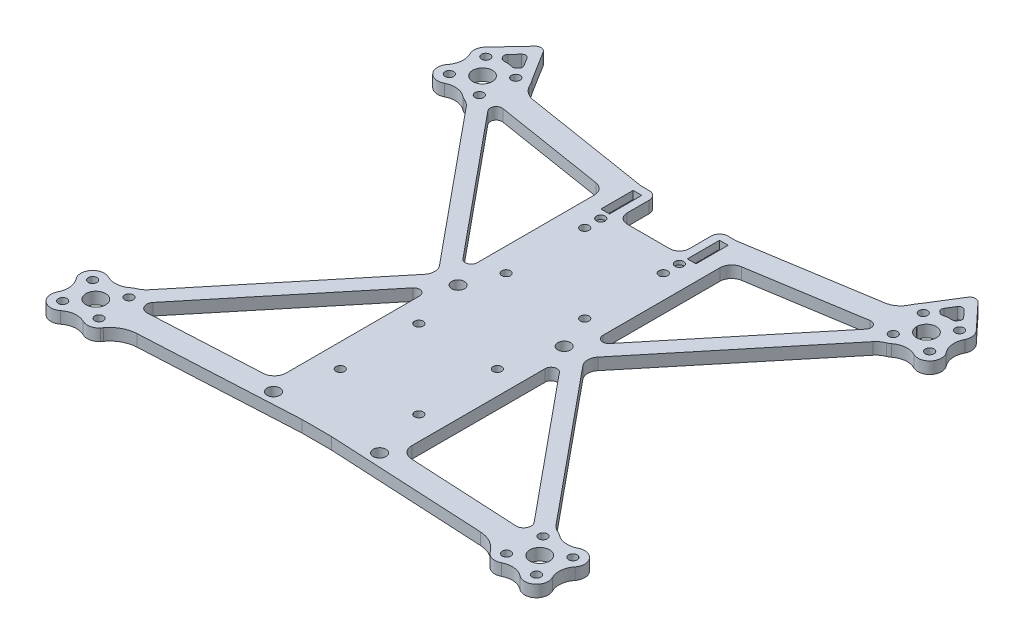
SolidWorks part; units mm, degrees
ref_plane "Front Plane" through (0, 0, 0) normal (0, 0, 1) x (1, 0, 0)
ref_plane "Top Plane" through (0, 0, 0) normal (0, 1, 0) x (1, 0, 0)
ref_plane "Right Plane" through (0, 0, 0) normal (1, 0, 0) x (0, 0, -1)
sketch "Sketch1" plane through (0, 0, 0) normal (0, 1, 0) x (1, 0, 0)
  line L0 (0, 42.225) -> (0, -42.225) construction
  line L1 (16, 42.225) -> (-16, 42.225)
  line L2 (16, 42.225) -> (16, -42.225)
  line L3 (16, -42.225) -> (-16, -42.225)
  line L4 (-16, 42.225) -> (-16, -42.225)
  line L5 (16, 42.225) -> (-16, -42.225) construction
  line L6 (16, -42.225) -> (-16, 42.225) construction
  line L12 (-12.1, 50.425) -> (-12.1, 52.425) construction
  line L17 (-11, 52.425) -> (-11, 42.225) construction
  line L18 (-7.9, 42.225) -> (-14.1, 42.225)
  line L20 (-10, 36) -> (10, 36)
  line L21 (-10, 36) -> (-10, 16)
  line L22 (-10, 16) -> (10, 16)
  line L23 (10, 36) -> (10, 16)
  line L24 (-10, 36) -> (10, 16) construction
  line L25 (-10, 16) -> (10, 36) construction
  line L26 (-14.5, 10.775) -> (14.5, 10.775)
  line L27 (-14.5, 10.775) -> (-14.5, 41.225)
  line L28 (-14.5, 41.225) -> (14.5, 41.225)
  line L29 (14.5, 10.775) -> (14.5, 41.225)
  line L30 (-14.5, 10.775) -> (14.5, 41.225) construction
  line L31 (-14.5, 41.225) -> (14.5, 10.775) construction
  line L32 (-10, -6.225) -> (10, -6.225)
  line L33 (-10, -6.225) -> (-10, -26.225)
  line L34 (-10, -26.225) -> (10, -26.225)
  line L35 (10, -6.225) -> (10, -26.225)
  line L36 (-10, -6.225) -> (10, -26.225) construction
  line L37 (-10, -26.225) -> (10, -6.225) construction
  line L38 (-15.75, -36.225) -> (15.75, -36.225)
  line L39 (-15.75, -36.225) -> (-15.75, 3.775)
  line L40 (-15.75, 3.775) -> (15.75, 3.775)
  line L41 (15.75, -36.225) -> (15.75, 3.775)
  line L42 (-15.75, -36.225) -> (15.75, 3.775) construction
  line L43 (-15.75, 3.775) -> (15.75, -36.225) construction
  line L48 (-7.9, 42.225) -> (-7.9, 52.425)
  line L49 (-7.9, 52.425) -> (-14.1, 52.425)
  line L59 (-14.1, 42.225) -> (-14.1, 52.425)
  line L63 (-12.1, 50.425) -> (-9.9, 50.425)
  line L64 (-12.1, 50.425) -> (-12.1, 42.225)
  line L65 (-12.1, 42.225) -> (-9.9, 42.225)
  line L66 (-9.9, 50.425) -> (-9.9, 42.225)
  line L67 (-12.1, 50.425) -> (-9.9, 42.225) construction
  line L68 (-12.1, 42.225) -> (-9.9, 50.425) construction
  line L69 (-12.1, 50.425) -> (-14.1, 50.425) construction
  line L74 (7.9, 42.225) -> (14.1, 42.225)
  line L75 (14.1, 42.225) -> (14.1, 52.425)
  line L76 (7.9, 52.425) -> (14.1, 52.425)
  line L77 (7.9, 42.225) -> (7.9, 52.425)
  line L78 (12.1, 50.425) -> (9.9, 50.425)
  line L79 (12.1, 50.425) -> (12.1, 42.225)
  line L80 (12.1, 42.225) -> (9.9, 42.225)
  line L81 (9.9, 50.425) -> (9.9, 42.225)
  line L82 (-14.5, 10.775) -> (-14.5, 3.775) construction
  line L83 (-14.5, 7.275) -> (16, 7.275) construction
  line L89 (-13.5, -37.225) -> (-16, -37.225) construction
  line L94 (-14.1, 52.425) -> (-16, 52.425)
  line L95 (-14.1, 52.425) -> (-14.1, 42.225)
  line L96 (-14.1, 42.225) -> (-16, 42.225)
  line L97 (-16, 52.425) -> (-16, 42.225)
  line L98 (14.1, 52.425) -> (16, 52.425)
  line L99 (14.1, 52.425) -> (14.1, 42.225)
  line L100 (14.1, 42.225) -> (16, 42.225)
  line L101 (16, 52.425) -> (16, 42.225)
  circle A3 centre (-10, 36) radius 1.1
  circle A4 centre (10, 36) radius 1.1
  circle A5 centre (10, 16) radius 1.1
  circle A6 centre (-10, 16) radius 1.1
  circle A7 centre (-10, -6.225) radius 1.1
  circle A8 centre (10, -6.225) radius 1.1
  circle A9 centre (10, -26.225) radius 1.1
  circle A10 centre (-10, -26.225) radius 1.1
  circle A37 centre (-13.5, 7.275) radius 2.5
  circle A38 centre (-13.5, 7.275) radius 1.625
  circle A39 centre (13.5, 7.275) radius 1.625
  circle A40 centre (-13.5, -39.725) radius 2.5
  circle A41 centre (-13.5, -39.725) radius 1.625
  circle A42 centre (13.5, -39.725) radius 1.625
  point P0 (0, 0)
  point P8 (0, 0)
  point P16 (0, 26)
  point P26 (0, 26)
  point P31 (0, -16.225)
  point P36 (0, -16.225)
  point P61 (-11, 46.325)
  dimension "D3" = 2
  dimension "D17" = 2.2
  dimension "D22" = 5
  dimension "D23" = 3.25
  dimension "D8" = 32
  dimension "D9" = 22
  dimension "D10" = 20
  dimension "D11" = 29
  dimension "D12" = 30.45
  dimension "D13" = 40
  dimension "D14" = 31.5
  dimension "D15" = 1
  dimension "D16" = 7
  dimension "D18" = 2.2
  dimension "D20" = 8.2
  dimension "D24" = 1
extrude "Base shape" add sketch "Sketch1" along normal blind 2 contours L63 L66 L1 L48 L49 L59 L18 L64 | L81 L78 L79 L1 L75 L76 L77 | L94 L97 L1 L59 | L101 L98 L75 L1 | L1 L4 L3 L2 | A4 | A3 | A7 | A8 | A9 | A10 | A5 | A6 | A39 | A38 | A41 | A42 region at (15.05, 0, -47.325) region at (13.1, 0, -42.3444) region at (-8.9, 0, -42.3444) region at (-15.05, 0, -47.325)
sketch "Sketch2" plane through (0, 0, 0) normal (0, -1, 0) x (1, 0, 0)
  line L0 (-12.1, -42.225) -> (-9.9, -50.425) construction
  line L1 (12.1, -42.225) -> (9.9, -50.425) construction
  line L4 (12.1, -42.225) -> (9.9, -42.225)
  line L5 (12.1, -50.425) -> (12.1, -42.225)
  line L6 (9.9, -50.425) -> (12.1, -50.425)
  line L7 (9.9, -42.225) -> (9.9, -50.425)
  line L8 (12.1, -42.225) -> (9.9, -42.225)
  line L9 (12.1, -50.425) -> (12.1, -42.225)
  line L10 (9.9, -50.425) -> (12.1, -50.425)
  line L11 (9.9, -42.225) -> (9.9, -50.425)
  line L12 (-9.9, -42.225) -> (-12.1, -42.225)
  line L13 (-9.9, -50.425) -> (-9.9, -42.225)
  line L14 (-12.1, -50.425) -> (-9.9, -50.425)
  line L15 (-12.1, -42.225) -> (-12.1, -50.425)
  line L16 (-9.9, -42.225) -> (-12.1, -42.225)
  line L17 (-9.9, -50.425) -> (-9.9, -42.225)
  line L18 (-12.1, -50.425) -> (-9.9, -50.425)
  line L19 (-12.1, -42.225) -> (-12.1, -50.425)
  circle A0 centre (-11, -46.325) radius 1.1
  circle A1 centre (11, -46.325) radius 1.1
  dimension "D1" = 0
  dimension "D2" = 0
extrude "Camera mount pockets" add sketch "Sketch2" against normal offset from surface (1 mm away) 1 contours A0 L19 | A0 L17 | A1 L9 | A1 L11 region at (11, 0, -43.8523) region at (11, 0, -48.7977) region at (-11, 0, -43.8523) region at (-11, 0, -48.7977) up to face at (11, 2, -46.325)
fillet "Main fillets" radius 2.5 6 edges at (7.9, 1, -42.225) (-7.9, 1, -42.225) (-16, 1, -52.425) (16, 1, -52.425) (-16, 1, 42.225) (16, 1, 42.225)
fillet "Inner camera mount fillets" radius 2.1 2 edges at (-7.9, 1, -52.425) (7.9, 1, -52.425)
sketch "Sketch3" plane through (0, 2, 0) normal (0, 1, 0) x (1, 0, 0)
  line L6 (12.1, 42.225) -> (12.1, 50.425)
  line L7 (9.9, 42.225) -> (12.1, 42.225)
  line L8 (-10, 52.425) -> (-13.5, 52.425)
  line L9 (-16, 49.925) -> (-16, -39.725)
  line L10 (-13.5, -42.225) -> (13.5, -42.225)
  line L11 (16, -39.725) -> (16, 49.925)
  line L12 (13.5, 52.425) -> (10, 52.425)
  line L13 (7.9, 50.325) -> (7.9, 44.725)
  line L14 (5.4, 42.225) -> (-5.4, 42.225)
  line L15 (-7.9, 44.725) -> (-7.9, 50.325)
  line L16 (-10, 52.425) -> (-13.5, 52.425)
  line L17 (-16, 49.925) -> (-16, -39.725)
  line L18 (-13.5, -42.225) -> (13.5, -42.225)
  line L19 (16, -39.725) -> (16, 49.925)
  line L20 (13.5, 52.425) -> (10, 52.425)
  line L21 (7.9, 50.325) -> (7.9, 44.725)
  line L22 (5.4, 42.225) -> (-5.4, 42.225)
  line L23 (-7.9, 44.725) -> (-7.9, 50.325)
  line L24 (9.9, 50.425) -> (9.9, 42.225)
  line L25 (12.1, 50.425) -> (9.9, 50.425)
  line L26 (12.1, 42.225) -> (12.1, 50.425)
  line L27 (9.9, 42.225) -> (12.1, 42.225)
  line L28 (9.9, 50.425) -> (9.9, 42.225)
  line L29 (12.1, 50.425) -> (9.9, 50.425)
  line L30 (-9.9, 42.225) -> (-9.9, 50.425)
  line L31 (-12.1, 42.225) -> (-9.9, 42.225)
  line L32 (-12.1, 50.425) -> (-12.1, 42.225)
  line L33 (-9.9, 50.425) -> (-12.1, 50.425)
  line L34 (-9.9, 42.225) -> (-9.9, 50.425)
  line L35 (-12.1, 42.225) -> (-9.9, 42.225)
  line L36 (-12.1, 50.425) -> (-12.1, 42.225)
  line L37 (-9.9, 50.425) -> (-12.1, 50.425)
  circle A0 centre (13.5, -39.725) radius 1.625 construction
  circle A1 centre (-13.5, -39.725) radius 1.625 construction
  circle A2 centre (-13.5, 7.275) radius 1.625 construction
  circle A3 centre (-10, -6.225) radius 1.1 construction
  circle A4 centre (-10, -26.225) radius 1.1 construction
  circle A5 centre (10, -26.225) radius 1.1 construction
  circle A6 centre (10, -6.225) radius 1.1 construction
  circle A7 centre (13.5, 7.275) radius 1.625 construction
  arc A8 (-13.5, 52.425) -> (-16, 49.925) centre (-13.5, 49.925) ccw
  arc A9 (-16, -39.725) -> (-13.5, -42.225) centre (-13.5, -39.725) ccw
  arc A10 (13.5, -42.225) -> (16, -39.725) centre (13.5, -39.725) ccw
  arc A11 (16, 49.925) -> (13.5, 52.425) centre (13.5, 49.925) ccw
  arc A12 (-7.9, 50.325) -> (-10, 52.425) centre (-10, 50.325) ccw
  arc A13 (5.4, 42.225) -> (7.9, 44.725) centre (5.4, 44.725) ccw
  arc A14 (-7.9, 44.725) -> (-5.4, 42.225) centre (-5.4, 44.725) ccw
  arc A15 (-7.9, 50.325) -> (-10, 52.425) centre (-10, 50.325) ccw
  arc A16 (-13.5, 52.425) -> (-16, 49.925) centre (-13.5, 49.925) ccw
  arc A17 (-16, -39.725) -> (-13.5, -42.225) centre (-13.5, -39.725) ccw
  arc A18 (13.5, -42.225) -> (16, -39.725) centre (13.5, -39.725) ccw
  arc A19 (16, 49.925) -> (13.5, 52.425) centre (13.5, 49.925) ccw
  arc A21 (5.4, 42.225) -> (7.9, 44.725) centre (5.4, 44.725) ccw
  arc A22 (-7.9, 44.725) -> (-5.4, 42.225) centre (-5.4, 44.725) ccw
  circle A24 centre (-10, 16) radius 1.1 construction
  circle A25 centre (-10, 36) radius 1.1 construction
  circle A26 centre (10, 36) radius 1.1 construction
  circle A27 centre (10, 16) radius 1.1 construction
  circle A28 centre (10, 16) radius 1.1
  circle A29 centre (10, 36) radius 1.1
  circle A30 centre (-10, 36) radius 1.1
  circle A31 centre (-10, 16) radius 1.1
  circle A32 centre (13.5, 7.275) radius 1.625
  circle A33 centre (10, -6.225) radius 1.1
  circle A34 centre (10, -26.225) radius 1.1
  circle A35 centre (-10, -26.225) radius 1.1
  circle A36 centre (-10, -6.225) radius 1.1
  circle A37 centre (13.5, -39.725) radius 1.625
  circle A38 centre (-13.5, -39.725) radius 1.625
  circle A39 centre (-13.5, 7.275) radius 1.625
  arc A48 (10, 52.425) -> (7.9, 50.325) centre (10, 50.325) ccw
  arc A49 (10, 52.425) -> (7.9, 50.325) centre (10, 50.325) ccw
  dimension "D1" = 0
  dimension "D2" = 0
  dimension "D3" = 0
extrude "Thicker base" add sketch "Sketch3" along normal blind 1
sketch "Sketch4" plane through (0, 0, 0) normal (0, -1, 0) x (1, 0, 0)
  line L0 (0, 13.9568) -> (0, -8.6953) construction
  line L1 (-14.1, -38.5) -> (-5.9, -38.5)
  line L2 (-14.1, -38.5) -> (-14.1, -41.7)
  line L3 (-14.1, -41.7) -> (-5.9, -41.7)
  line L4 (-5.9, -38.5) -> (-5.9, -41.7)
  line L5 (-10, -38.5) -> (-10, -41.7) construction
  line L7 (14.1, -38.5) -> (5.9, -38.5)
  line L8 (14.1, -38.5) -> (14.1, -41.7)
  line L9 (14.1, -41.7) -> (5.9, -41.7)
  line L10 (5.9, -38.5) -> (5.9, -41.7)
  line L11 (-14.1, -38.5) -> (-10.9, -41.7) construction
  line L12 (-14.1, -40.1) -> (-5.9, -40.1) construction
  circle A0 centre (-10, -36) radius 2
  circle A1 centre (-13.3929, -39.2071) radius 1
  circle A2 centre (-13.3929, -40.9929) radius 1
  circle A3 centre (-6.6071, -39.2071) radius 1
  circle A4 centre (-6.6071, -40.9929) radius 1
  circle A5 centre (6.6071, -40.9929) radius 1
  circle A6 centre (6.6071, -39.2071) radius 1
  circle A7 centre (13.3929, -39.2071) radius 1
  circle A8 centre (13.3929, -40.9929) radius 1
  point P9 (-10, -38)
  dimension "D5" = 4
  dimension "D7" = 2
  dimension "D1" = 8.2
  dimension "D2" = 3.2
  dimension "D3" = 10
  dimension "D4" = 0.5
  dimension "D6" = 45
extrude "Battery holder pockets" cut sketch "Sketch4" against normal offset from surface (2 mm away) 1 contours A2 L2 | A2 L3 | L2 A1 | L1 A1 | A3 L4 | A3 L1 | L4 A4 | L3 A4 | A5 L9 | A5 L10 | L10 A6 | L7 A6 | A7 L7 | A7 L8 | L8 A8 | L9 A8 | L3 L4 L1 L2 | L9 L10 L7 L8 region at (-13.3929, 0, -38.3812) region at (-14.2188, 0, -39.2071) region at (-6.6071, 0, -38.3812) region at (-14.2188, 0, -40.9929) region at (-5.7812, 0, -39.2071) region at (-13.3929, 0, -41.8188) region at (-6.6071, 0, -41.8188) region at (-5.7812, 0, -40.9929) region at (14.2188, 0, -39.2071) region at (13.3929, 0, -38.3812) region at (6.6071, 0, -38.3812) region at (14.2188, 0, -40.9929) region at (5.7812, 0, -39.2071) region at (13.3929, 0, -41.8188) region at (6.6071, 0, -41.8188) region at (5.7812, 0, -40.9929) up to face at (-13.5, 3, 41.35)
sketch "Sketch5" plane through (0, 2, 0) normal (0, -1, 0) x (1, 0, 0)
  line L0 (-10, -38.5) -> (-10, -41.7) construction
  line L1 (-12.6858, -38.5) -> (-7.3142, -38.5) construction
  line L2 (-12.6858, -41.7) -> (-7.3142, -41.7) construction
  line L3 (0, 5.9884) -> (0, -5.6723) construction
  circle A0 centre (-10, -40.1) radius 1.1
  circle A1 centre (10, -40.1) radius 1.1
  dimension "D1" = 2.2
extrude "Battery holder holes" cut sketch "Sketch5" against normal up to next
sketch "Sketch6" [suppressed] plane through (0, 0, 0) normal (0, -1, 0) x (1, 0, 0)
  line L0 (0, -5.1) -> (0, 9.653) construction
  line L8 (-13.5, -7.275) -> (13.5, -7.275) construction
  line L10 (-16, -25.775) -> (16, -25.775) construction
  line L11 (-16, -49.925) -> (-16, 39.725) construction
  line L12 (16, -49.925) -> (16, 39.725) construction
  line L13 (17.5, -34.275) -> (19, -34.275)
  line L14 (16, -37.275) -> (19, -37.275)
  line L15 (16, -37.275) -> (16, -14.275)
  line L16 (16, -14.275) -> (19, -14.275)
  line L17 (19, -37.275) -> (19, -14.275)
  line L18 (16, -37.275) -> (19, -14.275) construction
  line L19 (16, -14.275) -> (19, -37.275) construction
  line L20 (16, -35.775) -> (17.5, -35.775)
  line L21 (16, -35.775) -> (16, -15.775)
  line L22 (16, -15.775) -> (17.5, -15.775)
  line L23 (17.5, -35.775) -> (17.5, -15.775)
  line L24 (16, -35.775) -> (17.5, -15.775) construction
  line L25 (16, -15.775) -> (17.5, -35.775) construction
  line L26 (17.5, -17.275) -> (19, -17.275)
  line L27 (-17.5, -34.275) -> (-19, -34.275)
  line L28 (-17.5, -17.275) -> (-19, -17.275)
  line L29 (-16, -35.775) -> (-16, -15.775)
  line L30 (-16, -35.775) -> (-17.5, -35.775)
  line L31 (-17.5, -35.775) -> (-17.5, -15.775)
  line L32 (-16, -15.775) -> (-17.5, -15.775)
  line L33 (-16, -37.275) -> (-16, -14.275)
  line L34 (-16, -37.275) -> (-19, -37.275)
  line L35 (-19, -37.275) -> (-19, -14.275)
  line L36 (-16, -14.275) -> (-19, -14.275)
  line L37 (16, 22.725) -> (19, 22.725)
  line L38 (16, 22.725) -> (16, -0.275)
  line L39 (16, -0.275) -> (19, -0.275)
  line L40 (19, 22.725) -> (19, -0.275)
  line L41 (16, 21.225) -> (17.5, 21.225)
  line L42 (16, 21.225) -> (16, 1.225)
  line L43 (16, 1.225) -> (17.5, 1.225)
  line L44 (17.5, 21.225) -> (17.5, 1.225)
  line L45 (17.5, 2.725) -> (19, 2.725)
  line L46 (17.5, 19.725) -> (19, 19.725)
  line L47 (-17.5, 19.725) -> (-19, 19.725)
  line L48 (-17.5, 2.725) -> (-19, 2.725)
  line L49 (-16, 21.225) -> (-16, 1.225)
  line L50 (-16, 21.225) -> (-17.5, 21.225)
  line L51 (-17.5, 21.225) -> (-17.5, 1.225)
  line L52 (-16, 1.225) -> (-17.5, 1.225)
  line L53 (-16, 22.725) -> (-16, -0.275)
  line L54 (-16, 22.725) -> (-19, 22.725)
  line L55 (-19, 22.725) -> (-19, -0.275)
  line L56 (-16, -0.275) -> (-19, -0.275)
  point P19 (17.5, -25.775)
  point P25 (16.75, -25.775)
  line M18 (16, -49.925) -> (16, 39.725)
  line M22 (-16, 39.725) -> (-16, -49.925)
  dimension "D1" = 14
  dimension "D4" = 23
  dimension "D5" = 3
  dimension "D6" = 1.5
  dimension "D7" = 20
  dimension "D8" = 1.5
extrude "Strap holders" [suppressed] add sketch "Sketch6" against normal up to surface (2 mm away) contours L23 L20 L14 L17 L13 M18 | L23 L26 L17 L16 L22 M18 | L45 L44 L43 L39 L40 M18 | L44 L46 L40 L37 L38 L41 | L54 L55 L47 L51 L50 M22 | L56 L52 L51 L48 L55 M22 | L36 L35 L28 L31 L32 M22 | L35 L34 L30 L31 L27 M22 up to face at (-10, 2, -41.2)
fillet "Strap holder fillets" [suppressed] radius 0.75
sketch "Sketch7" plane through (0, 3, 0) normal (0, 1, 0) x (1, 0, 0)
  line L0 (-56.5, 56.5) -> (-16, 50.0116) construction
  line L1 (56.5, -56.5) -> (-56.5, -56.5)
  line L2 (56.5, -56.5) -> (56.5, 56.5)
  line L3 (56.5, 56.5) -> (-56.5, 56.5)
  line L4 (-56.5, -56.5) -> (-56.5, 56.5)
  line L5 (56.5, -56.5) -> (-56.5, 56.5) construction
  line L6 (56.5, 56.5) -> (-56.5, -56.5) construction
  line L7 (-16, 49.925) -> (-16, -39.725) construction
  line L8 (-56.9746, 53.5378) -> (-16.4746, 47.0493)
  line L9 (-47.647, 58.1199) -> (-12.1, 52.425)
  line L10 (-56.0254, 59.4622) -> (-15.5254, 52.9738) construction
  line L11 (-13.5, 7.275) -> (13.5, 7.275) construction
  line L12 (-63.45, 50.7819) -> (-49.55, 62.2181) construction
  line L13 (-56.5, 56.5) -> (-16, 7.275) construction
  line L14 (-58.0444, 55.2293) -> (-17.5444, 6.0043)
  line L15 (-54.9556, 57.7707) -> (-14.4556, 8.5457)
  line L16 (-17.5444, 6.0043) -> (-16, 4.1271)
  line L17 (-56.5, 56.5) -> (-60.3121, 61.1333) construction
  line L18 (-56.5, 65.5) -> (-56.5, 47.5) construction
  line L19 (-60.3121, 61.1333) -> (-51.8667, 60.3121) construction
  line L20 (-56.0894, 60.7227) -> (-55.3151, 68.6852) construction
  line L21 (-56.4116, 69.7087) -> (-62.3842, 63.31)
  line L22 (-54.0419, 69.4782) -> (-49.414, 62.0488)
  line L23 (-55.4603, 67.1922) -> (-58.7341, 63.6848)
  line L24 (-55.4603, 67.1922) -> (-52.9235, 63.1198)
  line L25 (-58.0444, -40.6793) -> (-17.5444, 8.5457)
  line L26 (-54.9556, -43.2207) -> (-14.4556, 6.0043)
  line L27 (-56.5, -41.95) -> (-13.5, -39.725) construction
  line L28 (-47.871, -44.5075) -> (-3.7595, -42.225)
  line L29 (-56.655, -38.954) -> (-16, -36.8503)
  line L30 (-56.345, -44.946) -> (-14.5762, -42.7847) construction
  line L31 (-56.5, -41.95) -> (-14.7312, -39.7887) construction
  line L32 (-13.5, -42.225) -> (13.5, -42.225) construction
  line L33 (-56.655, -38.954) -> (-14.8862, -36.7927) construction
  line L34 (-16.4746, 47.0493) -> (-16, 46.9733)
  line L35 (-12.1, 50.425) -> (-12.1, 52.425) construction
  line L36 (-10, 52.425) -> (-13.5, 52.425) construction
  circle A0 centre (-56.5, 56.5) radius 38.1
  circle A1 centre (-56.5, 56.5) radius 9
  circle A2 centre (-56.5, 56.5) radius 6
  circle A3 centre (-51.8667, 60.3121) radius 1.1
  circle A4 centre (-61.1333, 52.6879) radius 1.1
  circle A5 centre (-60.3121, 61.1333) radius 1.1
  circle A6 centre (-52.6879, 51.8667) radius 1.1
  circle A7 centre (-60.3121, 61.1333) radius 3
  circle A8 centre (-51.8667, 60.3121) radius 3
  circle A9 centre (-61.1333, 52.6879) radius 3
  circle A10 centre (-52.6879, 51.8667) radius 3
  circle A12 centre (-56.5, 56.5) radius 2.5
  circle A13 centre (-55.3151, 68.6852) radius 1.5
  circle A14 centre (-67.313, 57.5515) radius 4.864
  circle A15 centre (-57.5515, 45.687) radius 4.864
  circle A16 centre (-43.9819, 62.4587) radius 4.864
  circle A17 centre (-55.5501, 44.5421) radius 4.864
  circle A18 centre (-46.9606, 50.4143) radius 1.5
  circle A20 centre (-56.5, -41.95) radius 6
  circle A21 centre (-52.6879, -37.3167) radius 1.1
  circle A22 centre (-61.1333, -38.1379) radius 1.1
  circle A23 centre (-60.3121, -46.5833) radius 1.1
  circle A24 centre (-51.8667, -45.7621) radius 1.1
  circle A25 centre (-51.8667, -45.7621) radius 3
  circle A26 centre (-52.6879, -37.3167) radius 3
  circle A27 centre (-56.5, -41.95) radius 2.5
  circle A28 centre (-60.3121, -46.5833) radius 3
  circle A29 centre (-67.313, -43.0015) radius 4.864
  circle A30 centre (-61.1333, -38.1379) radius 3
  circle A31 centre (-57.5515, -31.137) radius 4.864
  circle A32 centre (-55.5501, -29.9921) radius 4.864
  circle A34 centre (-56.5, -41.95) radius 9
  circle A35 centre (-55.4485, -52.763) radius 4.864
  circle A38 centre (-43.36, -51.5674) radius 7.2836
  circle A39 centre (-47.0369, -36.5665) radius 1.8873
  point P0 (0, 0)
  point P36 (-52.6879, 51.8667)
  point P54 (-55.4603, 67.1922)
  point P111 (0, 0)
  point P112 (-11.9536, 52.425)
  point P115 (0, 0)
  point P116 (0, 0)
  arc M21 (-7.9, 50.325) -> (-10, 52.425) centre (-10, 50.325) ccw
  line M22 (-10, 52.425) -> (-13.5, 52.425)
  arc M23 (-13.5, 52.425) -> (-16, 49.925) centre (-13.5, 49.925) ccw
  line M24 (-16, 49.925) -> (-16, -39.725)
  arc M25 (-16, -39.725) -> (-13.5, -42.225) centre (-13.5, -39.725) ccw
  line M26 (-13.5, -42.225) -> (13.5, -42.225)
  dimension "D3" = 76.2
  dimension "D4" = 12
  dimension "D5" = 3
  dimension "D10" = 2.2
  dimension "D11" = 5
  dimension "D12" = 3
  dimension "D16" = 3
  dimension "D1" = 113
  dimension "D13" = 8
  dimension "D6" = 3
  dimension "D7" = 3
  dimension "D8" = 2
  dimension "D9" = 2
  dimension "D14" = 3
  dimension "D15" = 3
extrude "Arms" add sketch "Sketch7" against normal up to surface (3 mm away) contours A0 L8 L34 L9 M24 M23 M22 M21 | A1 L8 A0 L9 L3 | A10 L8 A1 L3 A2 | A16 L3 L9 | A8 A2 L3 A1 | A2 A8 A3 | A2 A8 A3 | A12 L3 A2 A8 A7 A9 L4 L14 | A12 L15 A10 A2 L3 | A12 L4 L8 A10 L15 | A12 L14 L8 L4 | A10 L8 L4 L14 | A10 L14 L4 A2 | L8 L14 L4 | A14 A9 A2 | A14 A2 A7 | A15 A2 A9 | A15 A10 A2 L4 | A10 L15 A1 L8 | A10 A1 L15 | A17 A1 L14 A10 | A10 L14 A1 | A17 L14 A1 | A1 L14 A0 L15 | A8 A1 L24 | A13 L24 A1 L22 | A13 | A13 L21 A1 L23 | A7 L23 A1 | A0 L14 L16 L15 M24 | L25 A34 L26 L16 L14 | L29 A34 L28 M26 M25 M24 | A39 L26 A34 | A39 A34 L29 | A34 L25 A26 | A34 A32 A26 L25 | A32 A34 L25 | A26 A31 L4 A20 | L4 A31 A20 | L25 A26 A20 L4 | A20 A30 A28 L4 A27 L25 | A20 A31 A30 | A20 A30 A29 | A20 A29 A28 | A35 L4 A20 A28 | A35 A25 A20 | L26 A27 L4 A20 A25 A26 | A35 A20 L4 | L4 A27 L26 A26 L29 | L29 A26 L25 L4 | L25 L29 L4 | L25 A27 L4 L29 | A38 L28 A34 | A34 L29 A26 A20 A25 | A34 L26 A26 L29 | A34 A26 L26 | A15 L4 A2 | A18 L8 A1 L15 | A1 L3 L9 | A7 | A5 | A9 | A4 | A10 | A6 | A26 | A21 | A30 | A22 | A28 | A23 | A25 | A24 region at (-47.184, 3, 45.066) region at (-31.3338, 3, 40.711) region at (-32.8289, 3, -52.5874) region at (-44.211, 3, -57.0386) region at (-17.1717, 3, -50.3538) region at (-48.9969, 3, 41.7471) region at (-49.1236, 3, -54.6581) region at (-48.8324, 3, -58.0351) region at (-47.1282, 3, -58.5028) region at (-24.1765, 3, -17.1136) region at (-41.5668, 3, -38.3497) region at (-57.4052, 3, 48.163) region at (-54.4445, 3, 47.8724) region at (-51.8807, 3, -55.6768) region at (-52.205, 3, -56.6697) region at (-49.2822, 3, -51.8002) region at (-48.4949, 3, -51.2849) region at (-52.3363, 3, -48.2332) region at (-34.0657, 3, 14.6748) region at (-56.355, 3, 47.9664) region at (-62.4224, 3, 44.0055) region at (-57.252, 3, 47.2609) region at (-55.1154, 3, 47.6835) region at (-48.0098, 3, 38.2823) region at (-49.1686, 3, 37.7777) region at (-54.4837, 3, -54.6883) region at (-53.0659, 3, -59.3254) region at (-50.9193, 3, -61.0916) region at (-49.7951, 3, -50.7418) region at (-52.9788, 3, -65.9755) region at (-52.3363, 3, 33.6832) region at (-52.9015, 3, -48.7171) region at (-52.1414, 3, -48.8113) region at (-49.026, 3, 36.4293) region at (-55.3151, 3, -68.6852) region at (-52.4447, 3, -63.9477) region at (-52.1414, 3, 34.2613) region at (-52.9015, 3, 34.1671) region at (-58.5555, 3, 36.0276) region at (-58.5555, 3, -50.5776) region at (-62.7075, 3, 41.0741) region at (-49.7951, 3, 36.1918) region at (-56.6984, 3, -53.811) region at (-55.8748, 3, -53.0321) region at (-58.1296, 3, -66.4764) region at (-55.5948, 3, 35.737) region at (-56.645, 3, 35.9336) region at (-56.645, 3, -50.4836) region at (-55.5948, 3, -50.287) region at (-62.7075, 3, -55.6241) region at (-56.701, 3, 39.2669) region at (-54.4356, 3, 40.1886) region at (-56.5346, 3, -53.4308) region at (-56.0913, 3, -51.6584) region at (-59.0444, 3, -64.5895) region at (-56.0913, 3, 37.1084) region at (-62.4224, 3, -58.5555) region at (-56.5412, 3, 38.9002) region at (-55.8564, 3, 38.5438) up to face at (10, 0, -40.1)
fillet "Motor protector fillets" radius 1 5 edges at (-52.9235, 1.5, -63.1198) (-54.2913, 1.5, -62.0787) (-57.5925, 1.5, -62.3997) (-58.7341, 1.5, -63.6848) (-55.4603, 1.5, -67.1922)
mirror "Arms mirror" about plane through (0, 0, 0) normal (1, 0, 0) of "Arms", "Motor protector fillets"
fillet "Arm fillets outer" radius 3 6 edges at (-16, 1.5, 36.8503) (-16, 1.5, -46.9733) (-18.5899, 1.5, -7.275) (16, 1.5, 36.8503) (18.5899, 1.5, -7.275) (16, 1.5, -46.9733)
fillet "Arm fillets inner" radius 1.5 4 edges at (-16, 1.5, -10.4229) (-16, 1.5, -4.1271) (16, 1.5, -4.1271) (16, 1.5, -10.4229)
